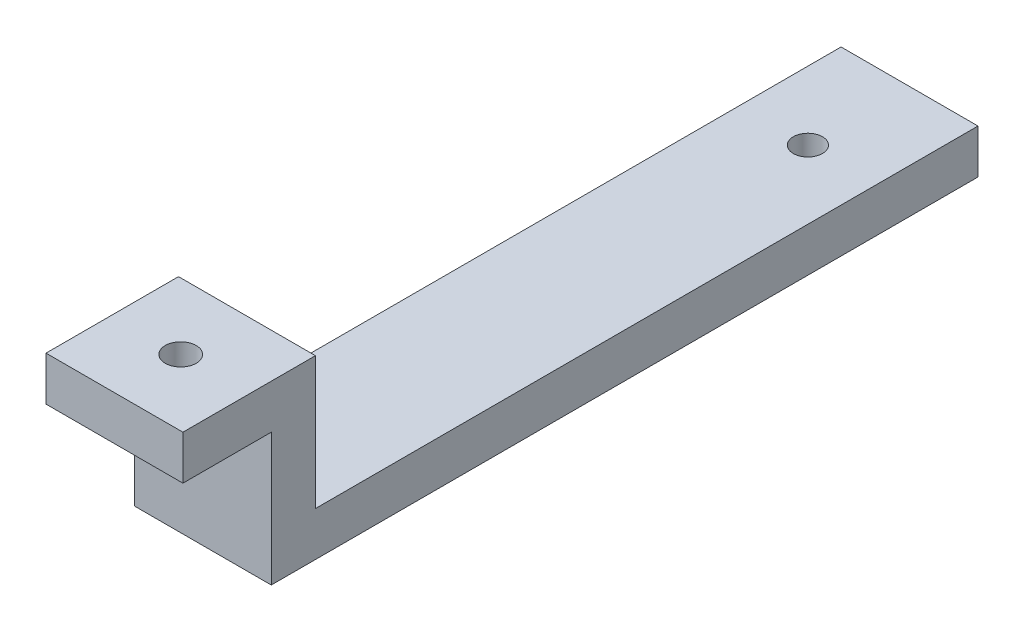
SolidWorks part; units mm, degrees
material "Galvanized Steel"
ref_plane "Front Plane" through (0, 0, 0) normal (0, 0, 1) x (1, 0, 0)
ref_plane "Top Plane" through (0, 0, 0) normal (0, 1, 0) x (1, 0, 0)
ref_plane "Right Plane" through (0, 0, 0) normal (1, 0, 0) x (0, 0, -1)
sketch "Sketch1" plane through (0, 0, 0) normal (1, 0, 0) x (0, 0, -1)
  line L0 (0, 0) -> (30, 0)
  line L1 (30, 0) -> (30, -29.972)
  line L2 (30, -29.972) -> (180, -29.972)
  dimension "D1" = 30
  dimension "D2" = 29.972
extrude "Extrude-Thin1" add sketch "Sketch1" along normal blind 31 thin contours L0 L1 L2 thin type one direction wall 10
sketch "Sketch6" plane through (0, 0, 0) normal (0, 1, 0) x (1, 0, 0)
  line L0 (0, 0) -> (0, 30) construction
  line L2 (31, 30) -> (0, 30) construction
  circle A0 centre (15.5, 15) radius 3.5
  dimension "D1" = 7
  dimension "D2" = 15.5
  dimension "D3" = 15
extrude "Cut-Extrude1" cut sketch "Sketch6" against normal blind 10
sketch "Sketch7" plane through (0, -29.972, 0) normal (0, 1, 0) x (1, 0, 0)
  line L0 (31, 30) -> (0, 30) construction
  line L2 (0, 30) -> (0, 180) construction
  circle A0 centre (15.494, 157) radius 3.302
  dimension "D1" = 6.604
  dimension "D3" = 15.494
  dimension "D2" = 127
extrude "Cut-Extrude3" cut sketch "Sketch7" against normal blind 10.16
